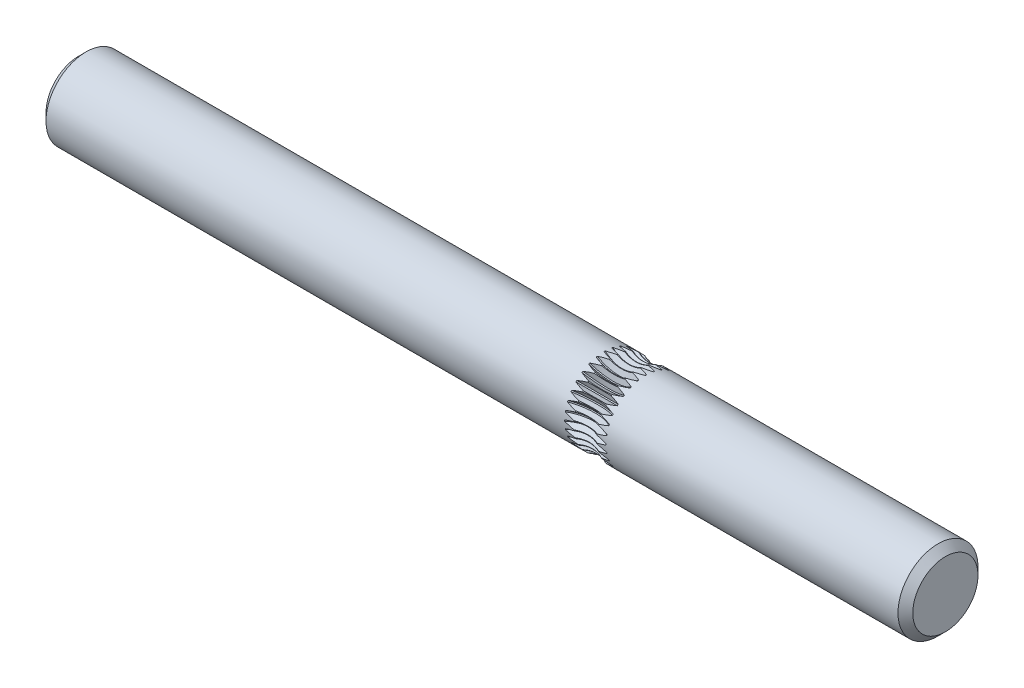
SolidWorks part; units mm, degrees
ref_plane "Plane1" through (0, 0, 0) normal (0, 0, 1) x (1, 0, 0)
ref_plane "Plane2" through (0, 0, 0) normal (0, 1, 0) x (1, 0, 0)
ref_plane "Plane3" through (0, 0, 0) normal (1, 0, 0) x (0, 0, -1)
ref_axis "Axis1" through (80.9, 0, 0) along (-1, 0, 0)
ref_plane "Plane4" through (41, 0, 0) normal (1, 0, 0) x (0, 0, -1)
sketch "BodySke" plane through (0, 0, 0) normal (0, 0, 1) x (1, 0, 0)
  line L1 (0, 0) -> (65, 0)
  line L2 (0, 0) -> (0, 3)
  line L3 (0, 3) -> (64.4455, 3)
  line L4 (65, 0) -> (65, 2.4455)
  line L6 (65, 2.4455) -> (64.4455, 3)
  line L7 (0, 0) -> (96.52, 0) construction
  line L8 (65, -2.4455) -> (64.4455, -3) construction
  line L9 (0, -3) -> (64.4455, -3) construction
  dimension "D1" = 65
  dimension "Body_ch_ang" = 45
  dimension "Diameter" = 6
  dimension "Minor_dia" = 4.891
revolve "BaseBody" add sketch "BodySke" angle 360 about L7
cosmetic thread "Cosmetic Thread1" parameters "D1"=19, "D2"=4.891
cosmetic thread "Cosmetic Thread2" parameters "D1"=12, "D2"=4.891
sketch "Sketch6" plane through (41, 0, 0) normal (1, 0, 0) x (0, 0, -1)
  line L0 (0, 2.421) -> (0, 2.8) construction
  line L1 (-0.175, 2.8) -> (0.175, 2.8) construction
  line L2 (-0.0437, 2.421) -> (0.0437, 2.421)
  line L3 (-2.9034, 4.8) -> (2.6646, 4.8) construction
  line L4 (0.0437, 2.421) -> (0.2626, 2.8)
  line L5 (-0.0437, 2.421) -> (-0.2626, 2.8)
  line L6 (0, 50) -> (0, -50) construction
  line L7 (-0.2626, 2.8) -> (-0.6224, 2.8)
  line L8 (-0.6224, 2.8) -> (-0.6224, 3.0829)
  line L9 (-0.6224, 3.0829) -> (0.4967, 3.0829)
  line L10 (-0.2626, 2.8) -> (0.2626, 2.8) construction
  line L11 (0.4967, 3.0829) -> (0.4967, 2.8)
  line L12 (0.4967, 2.8) -> (0.2626, 2.8)
  dimension "D1" = 0.0875
  dimension "D2" = 0.35
  dimension "D3" = 60
  dimension "D4" = 0.379
  dimension "D5" = 4.8
  dimension "D6" = 2
ref_plane "Plane5" through (14.5, 0, 0) normal (-1, 0, 0) x (0, 0, 1)
ref_plane "Plane6" through (53, 0, 0) normal (1, 0, 0) x (0, 0, -1)
sketch "Sketch7" plane through (14.5, 0, 0) normal (-1, 0, 0) x (0, 0, 1)
  circle A0 centre (0, 0) radius 2.4455
curve "Helix/Spiral1" pitch 0.7 height 18 turns 25.7143
sketch "ThdSchSke" plane through (0, 0, 0) normal (0, 0, 1) x (1, 0, 0)
  line L0 (14.5, -2.4455) -> (14.1117, -3)
  line L1 (14.5, -2.4455) -> (14.8883, -3)
  line L2 (14.8883, -3) -> (14.8883, -3.75)
  line L3 (-3.175, 0) -> (5.1513, 0) construction
  line L4 (14.5, 3.3) -> (14.5, -3.3) construction
  line L5 (14.8883, -3.75) -> (14.1117, -3.75)
  line L6 (14.1117, -3.75) -> (14.1117, -3)
  dimension "Thread_minor" = 4.891
  dimension "Diameter" = 6
  dimension "SideAngle" = 55
  dimension "VeeAngle" = 70
  dimension "Overcut" = 7.5
revolve "Cut-Revolve1" cut sketch "Sketch6" angle 360 about L3
pattern_circular "CirPattern1" count 32 over 360 about axis through (80.9, 0, 0) along (-1, 0, 0) of "Cut-Revolve1"
sweep "Cut-Sweep1" [suppressed] cut profiles "ThdSchSke" path "Helix/Spiral1"
sketch "Sketch8" plane through (0, 0, 0) normal (0, 0, 1) x (1, 0, 0)
  line L0 (53, -2.4455) -> (52.6117, -3)
  line L1 (53.3883, -3.75) -> (52.6117, -3.75)
  line L2 (52.6117, -3.75) -> (52.6117, -3)
  line L3 (53, -2.4455) -> (53.3883, -3)
  line L4 (53.3883, -3) -> (53.3883, -3.75)
  line L6 (0, 0) -> (75.6461, 0) construction
  line L7 (53, -2.6901) -> (53, 2.6901) construction
  dimension "D2" = 55
  dimension "D3" = 70
  dimension "D4" = 4.891
  dimension "D5" = 6
  dimension "D6" = 7.5
sketch "Sketch9" plane through (53, 0, 0) normal (1, 0, 0) x (0, 0, -1)
  circle A0 centre (0, 0) radius 3
curve "Helix/Spiral2" pitch 0.5 height 12.8571 turns 25.7143
sweep "Cut-Sweep2" [suppressed] cut profiles "Sketch8" path "Helix/Spiral2"
sketch "Sketch10" plane through (0, 0, 0) normal (0, 0, 1) x (1, 0, 0)
  line L0 (41, -50) -> (41, 50) construction
  circle A0 centre (41, 4.8) radius 2
  dimension "D1" = 4.8
  dimension "D2" = 4
revolve "Cut-Revolve2" cut sketch "Sketch10" angle 360 about axis through (80.9, 0, 0) along (-1, 0, 0)
chamfer "Chamfer1" distance 0.5545 angle 45 1 edges at (0, 0, 3)
